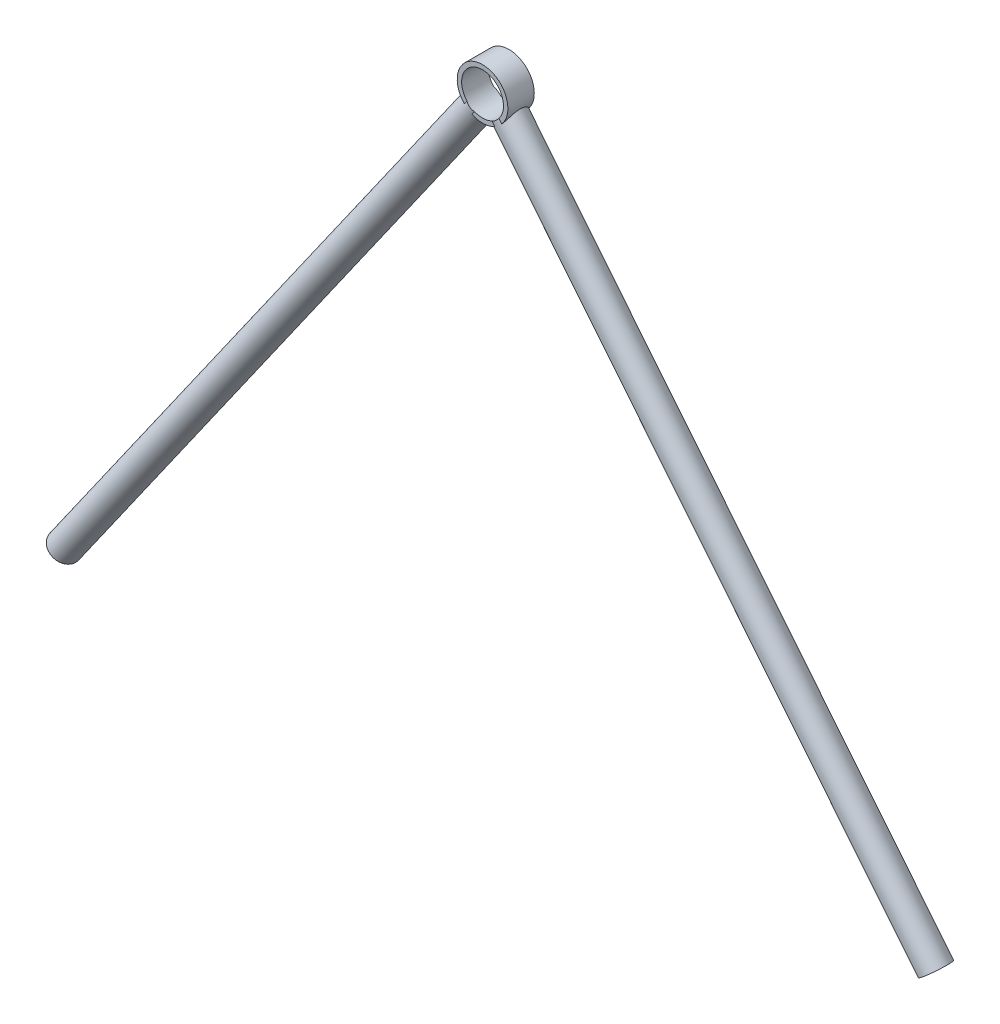
SolidWorks part; units mm, degrees
ref_plane "Front Plane" through (0, 0, 0) normal (0, 0, 1) x (1, 0, 0)
ref_plane "Top Plane" through (0, 0, 0) normal (0, 1, 0) x (1, 0, 0)
ref_plane "Right Plane" through (0, 0, 0) normal (1, 0, 0) x (0, 0, -1)
sketch3d "3DSketch1"
  line L0 (709.53, 565, 5) -> (487.75, 249.2, 5) construction
  line L1 (709.53, 565, 5) -> (487.75, 249.2, 5) construction
  line L2 (709.53, 565, 5) -> (513.3248, 285.6168, 5)
  line L3 (709.53, 565, 5) -> (709.53, 635, 5) construction
  dimension "D1" = 44.5
  dimension "D2" = 70
sketch3d "3DSketch2"
  line L0 (937.75, 282.79, 5) -> (709.53, 565, 5) construction
  line L1 (937.75, 282.79, 5) -> (709.53, 565, 5) construction
  line L2 (709.53, 565, 5) -> (909.7681, 317.3915, 5)
  dimension "D1" = 44.5
ref_plane "Plane1" through (0, 0, 5) normal (0, 0, 1) x (1, 0, 0)
sketch "Sketch1" plane through (0, 0, 5) normal (0, 0, 1) x (1, 0, 0)
  circle A0 centre (709.53, 565) radius 9.525
  circle A1 centre (709.53, 565) radius 11.525
  point P0 (709.53, 565)
  dimension "D1" = 19.05
  dimension "D2" = 2
extrude "Boss-Extrude1" add sketch "Sketch1" along normal mid plane 12
sweep "Sweep-Thin1" add path "3DSketch1" circular profile diameter 12.7 parameters "D1"=1, "D3"=12.7
sweep "Sweep-Thin2" add path "3DSketch2" circular profile diameter 12.7 parameters "D1"=1, "D3"=12.7
extrude "Cut-Extrude1" cut sketch "Sketch1<2>" against normal through all both and the other way through all contours A0 region at (709.53, 565, 5)
sketch "Sketch1<2>" plane through (0, 0, 5) normal (0, 0, 1) x (1, 0, 0) same geometry as "Sketch1"
